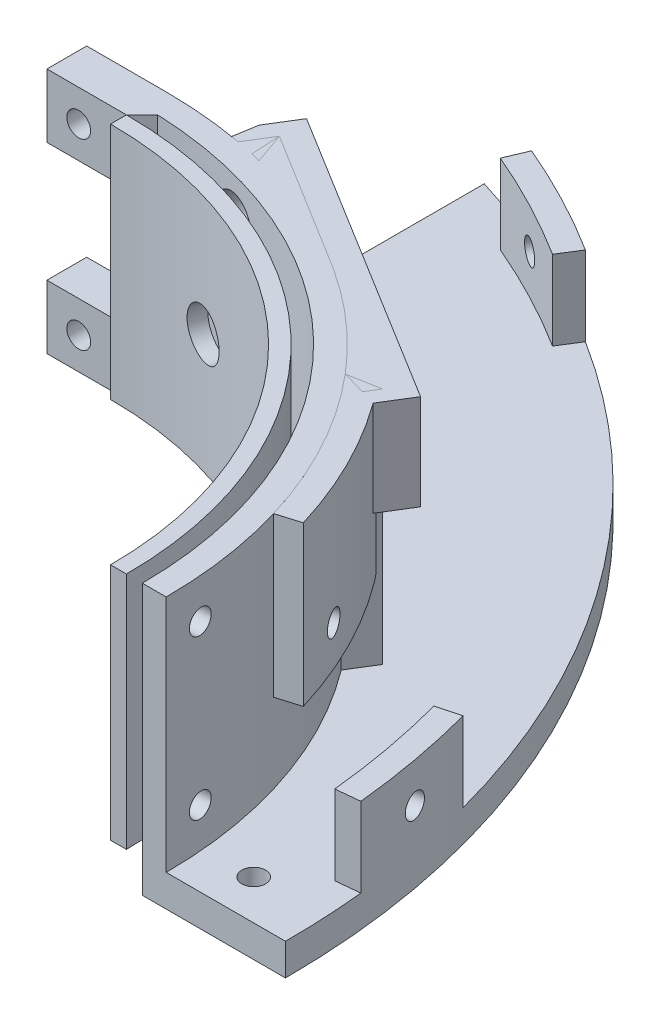
SolidWorks part; units mm, degrees
ref_plane "Front Plane" through (0, 0, 0) normal (0, 0, 1) x (1, 0, 0)
ref_plane "Top Plane" through (0, 0, 0) normal (0, 1, 0) x (1, 0, 0)
ref_plane "Right Plane" through (0, 0, 0) normal (1, 0, 0) x (0, 0, -1)
sketch "Sketch1" plane through (0, 0, 0) normal (0, 1, 0) x (1, 0, 0)
  line L0 (0, 0) -> (0, 2)
  line L1 (48, -48) -> (50, -48)
  line L2 (0, -48) -> (14.3468, -0.1025) construction
  line L3 (0, -48) -> (46, -28.4041) construction
  arc A0 (0, 2) -> (50, -48) centre (0, -48) cw
  arc A1 (0, 0) -> (48, -48) centre (0, -48) cw
  dimension "D1" = 50
  dimension "D2" = 2
  dimension "D3" = 2
  dimension "D4" = 50
  dimension "D5" = 14.5
  dimension "D7" = 20
extrude "Boss-Extrude1" add sketch "Sketch1" along normal mid plane 30
ref_plane "Plane1" through (14.3468, 0, 0.1025) normal (0.2869, 0, -0.9579) x (-0.9579, 0, -0.2869)
sketch "Sketch2" plane through (14.3468, 0, 0.1025) normal (0.2869, 0, -0.958) x (-0.9579, 0, -0.2869)
  line L0 (13.7729, 0) -> (-45.9816, 0) construction
  circle A0 centre (0, 0) radius 3.9
  dimension "D1" = 7.8
sketch "Sketch3" plane through (0, 0, 0) normal (0, 1, 0) x (1, 0, 0)
  line L0 (0, 4) -> (0, 7)
  line L1 (52, -48) -> (55, -48)
  line L2 (48, -48) -> (50, -48) construction
  arc A0 (0, 4) -> (52, -48) centre (0, -48) cw
  arc A1 (0, 7) -> (55, -48) centre (0, -48) cw
  dimension "D1" = 3
  dimension "D2" = 2
  dimension "D3" = 2
  dimension "D4" = 3
extrude "Boss-Extrude3" add sketch "Sketch3" along normal mid plane 30 separate body
extrude "Boss-Extrude4" add sketch "Sketch2" along normal up to surface and the other way up to surface up to face at (31.3848, 0, 16.6152) other way up to face at (30.1777, 0, 17.8223)
ref_plane "Plane2" through (46, 0, 28.4041) normal (0.92, 0, -0.3919) x (-0.3919, 0, -0.92)
sketch "Sketch4" plane through (46, 0, 28.4041) normal (0.92, 0, -0.3919) x (-0.3919, 0, -0.92)
  circle A0 centre (0, 0) radius 5.6
  dimension "D1" = 11.2
extrude "Boss-Extrude5" add sketch "Sketch4" along normal up to surface and the other way up to surface up to face at (31.3848, 0, 16.6152) other way up to face at (30.1777, 0, 17.8223)
sketch "Sketch5" plane through (14.3468, 0, 0.1025) normal (0.2869, 0, -0.958) x (-0.9579, 0, -0.2869)
  circle A0 centre (0, 0) radius 1.5
  dimension "D1" = 3
extrude "Cut-Extrude1" cut sketch "Sketch5" against normal through all and the other way through all
sketch "Sketch6" plane through (14.3468, 0, 0.1025) normal (0.2869, 0, -0.958) x (-0.9579, 0, -0.2869)
  circle A0 centre (0, 0) radius 3
  dimension "D1" = 6
extrude "Cut-Extrude2" cut sketch "Sketch6" against normal through all
sketch "Sketch7" plane through (46, 0, 28.4041) normal (0.92, 0, -0.3919) x (-0.3919, 0, -0.92)
  circle A0 centre (0, 0) radius 1.5
  dimension "D1" = 3
extrude "Cut-Extrude3" cut sketch "Sketch7" against normal through all both and the other way through all
sketch "Sketch8" plane through (46, 0, 28.4041) normal (0.92, 0, -0.3919) x (-0.3919, 0, -0.92)
  circle A0 centre (0, 0) radius 3
  dimension "D1" = 6
extrude "Cut-Extrude4" cut sketch "Sketch8" against normal through all
sketch "Sketch9" plane through (0, -15, 0) normal (0, 1, 0) x (1, 0, 0)
  line L0 (0, 4) -> (0, 47)
  line L1 (52, -48) -> (70, -48)
  line L2 (70, -48) -> (70, 47) construction
  line L3 (70, 47) -> (0, 47) construction
  arc A1 (0, 4) -> (52, -48) centre (0, -48) cw
  arc A2 (52, -48) -> (0, 4) centre (0, -48) ccw construction
  arc A3 (0, 47) -> (70, -48) centre (-29.4643, -48) cw
  dimension "D1" = 40
  dimension "D2" = 15
extrude "Boss-Extrude6" add sketch "Sketch9" against normal blind 4
sketch "Sketch12" plane through (0, -19, 0) normal (0, 1, 0) x (1, 0, 0)
  line L5 (0, 25.5) -> (5, 25.5) construction
  line L7 (61, -43) -> (61, -48) construction
  line L9 (0, 47) -> (0, 4) construction
  line L10 (52, -48) -> (70, -48) construction
  circle A2 centre (5, 25.5) radius 1.5
  circle A3 centre (61, -43) radius 1.5
  dimension "D4" = 3
  dimension "D5" = 5
extrude "Cut-Extrude6" cut sketch "Sketch12" along normal through all
sketch "Sketch19" plane through (0, -15, 0) normal (0, -1, 0) x (1, 0, 0)
  line L0 (69.4973, 38.0126) -> (66.5125, 38.3139)
  line L2 (8.2183, -40.7997) -> (9.3902, -43.5613)
  line L3 (66.6155, 22.2743) -> (63.7176, 23.0502)
  line L4 (21.9689, -33.6087) -> (23.5685, -36.1467)
  line L5 (-29.4643, 48) -> (66.5125, 38.3139) construction
  line L6 (8.2183, -40.7997) -> (-29.4643, 48) construction
  arc A0 (69.4973, 38.0126) -> (66.6155, 22.2743) centre (-29.4643, 48) cw
  arc A1 (0, -47) -> (70, 48) centre (-29.4643, 48) ccw construction
  arc A2 (66.5125, 38.3139) -> (63.7176, 23.0502) centre (-29.4643, 48) cw
  arc A3 (21.9689, -33.6087) -> (8.2183, -40.7997) centre (-29.4643, 48) cw
  arc A4 (23.5685, -36.1467) -> (9.3902, -43.5613) centre (-29.4643, 48) cw
  dimension "D1" = 10
  dimension "D2" = 3
  dimension "D3" = 16
  dimension "D4" = 16
  dimension "D5" = 10
  dimension "D6" = 3
extrude "Boss-Extrude7" add sketch "Sketch19" against normal blind 10
sketch "Sketch20" plane through (0, -5, 0) normal (0, 1, 0) x (-1, 0, 0)
  line L0 (-68.3734, 30.0854) -> (29.4643, 48) construction
  line L1 (29.4643, 48) -> (-16.6287, -40.1396) construction
  arc A0 (-69.4973, 38.0126) -> (-66.6155, 22.2743) centre (29.4643, 48) ccw construction
  arc A1 (-23.5685, -36.1467) -> (-9.3902, -43.5613) centre (29.4643, 48) ccw construction
ref_plane "Plane3" through (16.6287, -5, -40.1396) normal (0.4634, 0, -0.8861) x (-0.8861, 0, -0.4634)
sketch "Sketch21" plane through (16.6287, -5, -40.1396) normal (0.4634, 0, -0.8861) x (-0.8861, 0, -0.4634)
  line L0 (-8, -10) -> (8, -10) construction
  line L1 (8, 0) -> (8, -10) construction
  line L2 (0, -10) -> (0, 0) construction
  line L3 (-78.3963, 0) -> (0, 0) construction
  circle A0 centre (0, -5) radius 1.5
  dimension "D1" = 3
extrude "Cut-Extrude10" cut sketch "Sketch21" against normal up to surface (3.0117 mm away) up to face at (15.166, -10, -37.3427)
ref_plane "Plane4" through (68.3734, -5, 30.0854) normal (0.9836, 0, -0.1801) x (-0.1801, 0, -0.9836)
sketch "Sketch22" plane through (68.3734, -5, 30.0854) normal (0.9836, 0, -0.1801) x (-0.1801, 0, -0.9836)
  line L0 (8, -10) -> (-8, -10) construction
  line L2 (0, 0) -> (0, -10) construction
  line L3 (0, 0) -> (78.3963, 0) construction
  circle A0 centre (0, -5) radius 1.5
  dimension "D1" = 3
extrude "Cut-Extrude11" cut sketch "Sketch22" against normal up to surface (3.0117 mm away) up to face at (65.2688, -10, 30.6539)
sketch "Sketch23" plane through (0, 15, 0) normal (0, 1, 0) x (1, 0, 0)
  line L0 (0, -48) -> (8.9698, 6.2636) construction
  line L1 (8.9698, 6.2636) -> (9.4591, 9.2235)
  line L2 (0, -48) -> (52.6727, -32.1702) construction
  line L3 (52.6727, -32.1702) -> (55.5458, -31.3067)
  arc A0 (55, -48) -> (0, 7) centre (0, -48) ccw construction
  arc A1 (8.9698, 6.2636) -> (52.6727, -32.1702) centre (0, -48) cw
  arc A2 (9.4591, 9.2235) -> (55.5458, -31.3067) centre (0, -48) cw
  dimension "D1" = 3
  dimension "D2" = 9
  dimension "D3" = 16
extrude "Boss-Extrude8" add sketch "Sketch23" against normal blind 20 separate body
sketch "Sketch24" plane through (14.3468, 0, 0.1025) normal (0.2869, 0, -0.958) x (-0.9579, 0, -0.2869)
  circle A0 centre (0, 0) radius 1.5
  circle A1 centre (0, 0) radius 1.5 construction
extrude "Cut-Extrude12" cut sketch "Sketch24" along normal up to surface (7.9806 mm away) up to face at (35.4025, 5, 7.744)
sketch "Sketch25" plane through (46, 0, 28.4041) normal (0.92, 0, -0.3919) x (-0.3919, 0, -0.92)
  circle A0 centre (0, 0) radius 1.5
  circle A1 centre (0, 0) radius 1.5 construction
extrude "Cut-Extrude13" cut sketch "Sketch25" along normal up to surface (7.9806 mm away) up to face at (35.4025, 5, 7.744)
sketch "Sketch26" plane through (0, 15, 0) normal (0, 1, 0) x (1, 0, 0)
  line L0 (11.7352, 12.9121) -> (49.1801, -10.1937)
  line L1 (11.7352, 12.9121) -> (9.4591, 9.2235)
  line L2 (49.1801, -10.1937) -> (46.904, -13.8823)
  arc A1 (55.5458, -31.3067) -> (9.4591, 9.2235) centre (0, -48) ccw construction
  arc A2 (9.4591, 9.2235) -> (46.904, -13.8823) centre (0, -48) cw
  point P13 (30.4577, 1.3592)
  arc M5 (55.5458, -31.3067) -> (9.4591, 9.2235) centre (0, -48) ccw
  dimension "D1" = 44
extrude "Boss-Extrude9" add sketch "Sketch26" against normal blind 12 contours L0 L1 M5 | L2 L0 M5 | A2 L2 L0 L1 region at (43.857, 15, 8.4266) region at (15.7019, 15, -8.9468)
sketch "Sketch28" plane through (9.0065, 0, -14.5959) normal (0.5251, 0, -0.851) x (-0.851, 0, -0.5251)
  line L0 (-41.4563, 7) -> (-8.9563, 7) construction
  line L1 (-25.2063, 7) -> (-25.2063, 3) construction
  circle A0 centre (-41.4563, 7) radius 1
  circle A1 centre (-8.9563, 7) radius 1
  dimension "D1" = 32.5
  dimension "D2" = 2
  dimension "D3" = 4
extrude "Cut-Extrude14" cut sketch "Sketch28" against normal through all
sketch "Sketch29" plane through (9.0065, 0, -14.5959) normal (0.5251, 0, -0.851) x (-0.851, 0, -0.5251)
  circle A0 centre (-41.4563, 7) radius 2.5
  circle A1 centre (-8.9563, 7) radius 2.5
  dimension "D1" = 5
  dimension "D2" = 5
extrude "Cut-Extrude15" cut sketch "Sketch29" against normal up to surface (2.7465 mm away) from offset 2 up to face at (14.7458, 7.2259, -4.9864) offset against normal yes
sketch "Sketch30" plane through (0, 0, 0) normal (-1, 0, 0) x (0, 0, 1)
  line L0 (-7, 15) -> (-2, 15)
  line L1 (-2, 15) -> (-2, 7)
  line L3 (-2, 7) -> (-7, 7)
  line L4 (-7, 15) -> (-7, -15) construction
  line L5 (-7, 7) -> (-7, 15)
  line L6 (-7, -8) -> (-2, -8)
  line L7 (-2, -8) -> (-2, -16)
  line L8 (-2, -16) -> (-7, -16)
  line L9 (-7, -16) -> (-7, -8)
  dimension "D1" = 15
  dimension "D2" = 8
  dimension "D3" = 8
  dimension "D4" = 5
extrude "Boss-Extrude10" add sketch "Sketch30" along normal blind 10
sketch "Sketch31" plane through (0, 0, -7) normal (0, 0, -1) x (-1, 0, 0)
  line L0 (6, 11) -> (10, 11) construction
  line L1 (10, 15) -> (10, 7) construction
  line L2 (0, 15) -> (0, 7) construction
  line L3 (10, -12) -> (6, -12) construction
  line L4 (10, -8) -> (10, -16) construction
  circle A0 centre (6, 11) radius 1.5
  circle A1 centre (6, -12) radius 1.5
  dimension "D1" = 3
  dimension "D2" = 6
extrude "Cut-Extrude16" cut sketch "Sketch31" against normal up to surface (5 mm away) up to face at (-5, -12, -2)
sketch "Sketch32" plane through (0, 0, -7) normal (0, 0, -1) x (-1, 0, 0)
  circle A0 centre (6, 11) radius 3
  circle A1 centre (6, -12) radius 3
  dimension "D1" = 6
  dimension "D2" = 6
extrude "Cut-Extrude17" cut sketch "Sketch32" against normal blind 2
sketch "Sketch37" plane through (0, 15, 0) normal (0, 1, 0) x (1, 0, 0)
  line L0 (11.9402, 9.2925) -> (45.9523, -11.7593)
  line L1 (45.9523, -11.7593) -> (43.9707, -14.9609)
  line L2 (11.9402, 9.2925) -> (9.9586, 6.0909)
  arc A0 (55, -48) -> (0, 7) centre (0, -48) ccw construction
  arc A1 (55, -48) -> (0, 7) centre (0, -48) ccw construction
  arc A2 (9.9586, 6.0909) -> (43.9707, -14.9609) centre (0, -48) cw
  point P2 (28.9463, -1.2334)
  arc M7 (55, -48) -> (0, 7) centre (0, -48) ccw
  dimension "D1" = 40
  dimension "D2" = 10
extrude "Boss-Extrude11" add sketch "Sketch37" along normal up to surface (-30 mm away) contours L0 L2 M7 | L1 L0 M7 | A2 L1 L0 L2 region at (41.1396, 15, 10.1008) region at (15.5713, 15, -5.7248) up to face at (5, -15, -27)
sketch "Sketch33" plane through (0, 0, 0) normal (-1, 0, 0) x (0, 0, 1)
  line L0 (-7, 7) -> (-4, 7)
  line L1 (-4, 7) -> (-4, -8)
  line L2 (-4, -8) -> (-7, -8)
  line L3 (-7, -8) -> (-7, 7) construction
  line L4 (-7, 7) -> (-9.2925, 7)
  line L5 (-9.2925, -15) -> (-9.2925, 15) construction
  line L6 (-9.2925, 7) -> (-9.2925, -8)
  line L7 (-9.2925, -8) -> (-7, -8)
extrude "Cut-Extrude18" cut sketch "Sketch33" against normal through all
sketch "Sketch34" plane through (0, 0, -4) normal (0, 0, -1) x (-1, 0, 0)
  line L1 (-20.491, 7) -> (0, 7)
  line L2 (-20.491, 7) -> (-20.491, -8)
  line L3 (-20.491, -8) -> (0, -8)
  line L4 (0, 7) -> (0, -8)
  line L5 (-20.491, 7) -> (0, -8) construction
  line L6 (-20.491, -8) -> (0, 7) construction
  line L7 (17.9165, -8) -> (17.9165, 7) construction
  point P0 (-10.2455, -0.5)
extrude "Cut-Extrude19" cut sketch "Sketch34" against normal through all
fillet "Fillet1" radius 7.5 2 edges at (20.491, 7, -1.8962) (20.491, -8, -1.8962)
chamfer "Chamfer1" distance 2 angle 45 2 edges at (0, -12, -4) (0, 11, -4)
sketch "Sketch35" plane through (0, 15, 0) normal (0, 1, 0) x (1, 0, 0)
  line L0 (61, -43) -> (0, -48) construction
ref_plane "Plane5" through (50.908, 0, -4.1728) normal (0.9967, 0, -0.0817) x (-0.0817, 0, -0.9967)
sketch "Sketch36" plane through (50.908, 0, -4.1728) normal (0.9967, 0, -0.0817) x (-0.0817, 0, -0.9967)
  line L1 (-18.503, 15) -> (-52.3327, 15) construction
  circle A0 centre (-47.8396, 10) radius 1.5
  circle A1 centre (-47.8396, -10) radius 1.5
  dimension "D1" = 3
  dimension "D2" = 3
  dimension "D3" = 20
  dimension "D4" = 5
extrude "Cut-Extrude20" cut sketch "Sketch36" against normal through all
sketch "Sketch38" plane through (7.4658, 0, -12.062) normal (0.5263, 0, -0.8503) x (-0.8503, 0, -0.5263)
  line L0 (-25.2622, -15) -> (-25.2622, 0) construction
  line L1 (-40.2622, -10) -> (-10.2622, -10) construction
  line L2 (-40.2622, -10) -> (-40.2622, 10) construction
  line L3 (-40.2622, 10) -> (-10.2622, 10) construction
  line L4 (-10.2622, -10) -> (-10.2622, 10) construction
  line L5 (-40.2622, -10) -> (-10.2622, 10) construction
  line L6 (-40.2622, 10) -> (-10.2622, -10) construction
  line L7 (-5.2622, -15) -> (-45.2622, -15) construction
  line L8 (-25.2622, 0) -> (0, 0) construction
  line L9 (-45.2622, 0) -> (-25.2622, 0) construction
  line L10 (-45.2622, -15) -> (-45.2622, 15) construction
  circle A0 centre (-40.2622, 10) radius 1.5
  circle A1 centre (-10.2622, 10) radius 1.5
  circle A2 centre (-10.2622, -10) radius 1.5
  circle A3 centre (-40.2622, -10) radius 1.5
  point P0 (-25.2622, 0)
  dimension "D3" = 3
  dimension "D1" = 30
  dimension "D2" = 20
extrude "Cut-Extrude21" cut sketch "Sketch38" against normal up to surface (4.783 mm away) up to face at (51.925, 9.6557, 45.2087)
sketch "Sketch39" plane through (7.4658, 0, -12.062) normal (0.5263, 0, -0.8503) x (-0.8503, 0, -0.5263)
  circle A0 centre (-10.2622, 10) radius 3
  circle A1 centre (-10.2622, -10) radius 3
  circle A2 centre (-40.2622, -10) radius 3
  circle A3 centre (-40.2622, 10) radius 3
  dimension "D1" = 6
extrude "Cut-Extrude22" cut sketch "Sketch39" against normal up to surface (3.2148 mm away) from offset 3 up to face at (39.9561, -9.6562, 14.7208) offset against normal yes
